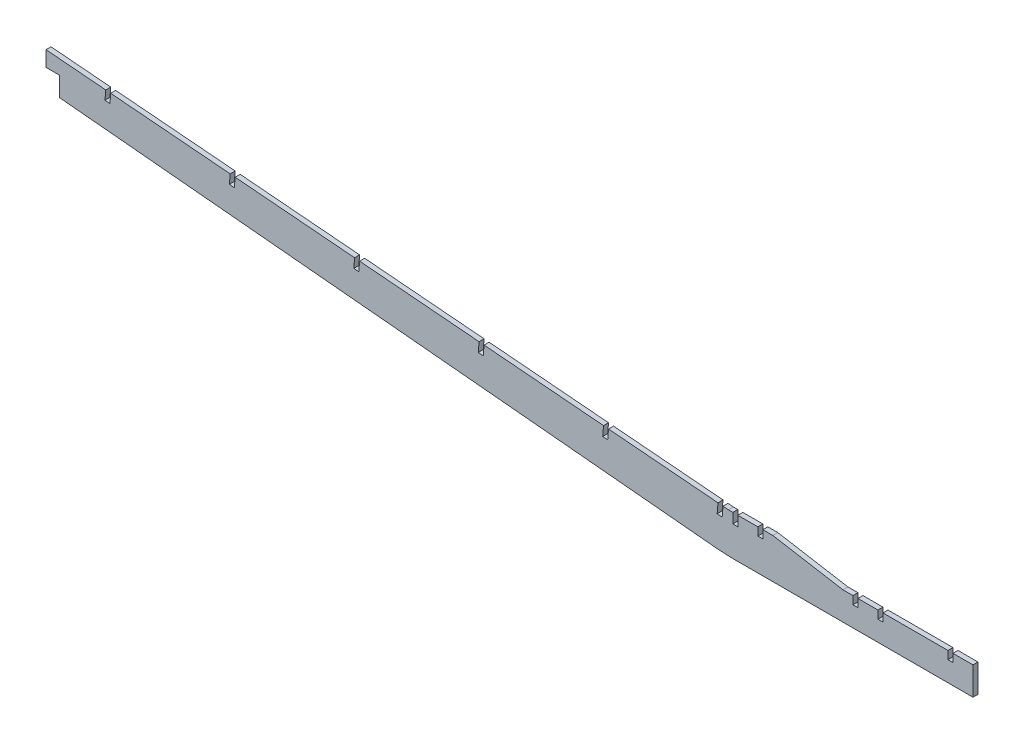
SolidWorks part; units mm, degrees
ref_plane "Front Plane" through (0, 0, 0) normal (0, 0, 1) x (1, 0, 0)
ref_plane "Top Plane" through (0, 0, 0) normal (0, 1, 0) x (1, 0, 0)
ref_plane "Right Plane" through (0, 0, 0) normal (1, 0, 0) x (0, 0, -1)
sketch "Sketch1" plane through (0, 0, 0) normal (0, 0, 1) x (1, 0, 0)
  line L0 (-951.0618, 63.2916) -> (-11.5367, -24.9026)
  line L8 (-8.3728, -25.1683) -> (-6.7788, -6.1851) construction
  line L9 (-6.7788, -6.1851) -> (-9.9426, -5.9194)
  line L10 (-9.9426, -5.9194) -> (-11.5367, -24.9026) construction
  line L11 (-11.5367, -24.9026) -> (-8.3728, -25.1683)
  line L12 (3.175, -25.5459) -> (3.175, -6.4959) construction
  line L13 (3.175, -6.4959) -> (0, -6.4959)
  line L14 (0, -6.4959) -> (0, -25.5459) construction
  line L15 (0, -25.5459) -> (3.175, -25.5459)
  line L17 (-943.9754, 109.7383) -> (-947.3666, 69.3536)
  line L19 (-8.3728, -25.1683) -> (0, -25.5459)
  line L20 (3.175, -25.5459) -> (152.4, -25.5459)
  line L21 (25.4, -0.1459) -> (69.85, -7.7659)
  line L22 (25.4, -0.1459) -> (-2.8123, -0.1459)
  line L23 (-2.8123, -0.1459) -> (-946.5481, 79.1019)
  line L24 (0, -6.4959) -> (0, -0.1459)
  line L25 (3.175, -6.4959) -> (3.175, -0.1459)
  line L26 (-6.7788, -6.1851) -> (-6.2474, 0.1426)
  line L27 (-9.9426, -5.9194) -> (-9.4113, 0.4083)
  line L28 (-9.9426, -5.9194) -> (-946.998, 73.7432)
  line L29 (69.85, -7.7659) -> (152.4, -7.7659)
  line L30 (152.4, -7.7659) -> (152.4, -25.5459)
  line L31 (76.2, -7.7659) -> (76.2, -25.5459)
  line L32 (79.375, -7.7659) -> (79.375, -25.5459)
  line L33 (76.2, -12.8459) -> (79.375, -12.8459)
  line L34 (15.875, -0.1459) -> (15.875, -5.2259)
  line L35 (15.875, -5.2259) -> (19.05, -5.2259)
  line L36 (19.05, -5.2259) -> (19.05, -0.1459)
  line L37 (92.075, -7.7659) -> (92.075, -12.8459)
  line L38 (92.075, -12.8459) -> (95.25, -12.8459)
  line L39 (95.25, -12.8459) -> (95.25, -7.7659)
  line L40 (136.525, -7.7659) -> (136.525, -12.8459)
  line L41 (136.525, -12.8459) -> (139.7, -12.8459)
  line L42 (139.7, -12.8459) -> (139.7, -7.7659)
  line L44 (-951.0618, 63.2916) -> (-950.5305, 69.6193)
  line L45 (-950.5305, 69.6193) -> (-947.3666, 69.3536)
  dimension "D1" = 25.4
  dimension "D2" = 6.35
extrude "Boss-Extrude1" add sketch "Sketch1" along normal blind 3.175 contours L31 L29 L21 L22 L25 L13 L24 L23 L26 L9 L28 L17 L11 L19 L15 L20 | L33 L31 L20 L32 | L29 L32 L20 L30 | L28 L27 L23 L17 | L45 L44 L17 region at (-380.2142, 18.2171, 0) region at (-465.2737, 35.7392, 0) region at (77.7875, -19.1959, 0) region at (115.8875, -16.8176, 0)
sketch "Sketch2" plane through (0, 0, 3.175) normal (0, 0, 1) x (1, 0, 0)
  line L1 (-73.9963, 64.5177) -> (-80.9723, -18.558)
  line L3 (-77.1601, 64.7834) -> (-84.1362, -18.2923)
  line L5 (-153.17, 68.7234) -> (-159.8855, -11.2491)
  line L7 (-232.3428, 72.9404) -> (-238.7996, -3.951)
  line L9 (-311.5203, 77.1018) -> (-317.7101, 3.3887)
  line L11 (-390.6978, 81.2631) -> (-396.6209, 10.7264)
  line L13 (-469.8812, 85.3537) -> (-475.5272, 18.1169)
  line L15 (-549.0652, 89.4374) -> (-554.4332, 25.5108)
  line L17 (-628.256, 93.4393) -> (-633.334, 32.9679)
  line L19 (-707.4489, 97.4177) -> (-712.2332, 40.4425)
  line L21 (-786.6506, 101.2897) -> (-791.1254, 48.0007)
  line L23 (-865.8569, 105.1088) -> (-870.014, 55.603)
  line L25 (-235.5067, 73.2061) -> (-241.9634, -3.6853)
  line L27 (-314.6841, 77.3675) -> (-320.874, 3.6544)
  line L29 (-393.8616, 81.5287) -> (-399.7848, 10.992)
  line L31 (-473.045, 85.6194) -> (-478.6911, 18.3826)
  line L33 (-552.229, 89.7031) -> (-557.5971, 25.7765)
  line L35 (-631.4199, 93.705) -> (-636.4978, 33.2336)
  line L37 (-710.6127, 97.6833) -> (-715.3971, 40.7082)
  line L39 (-789.8145, 101.5554) -> (-794.2893, 48.2664)
  line L41 (-9.9426, -5.9194) -> (-946.998, 73.7432)
  line L43 (-9.4113, 0.4083) -> (-946.5481, 79.1019)
  line L45 (-156.3339, 68.9891) -> (-163.0494, -10.9834)
  line L47 (-869.0207, 105.3745) -> (-873.1778, 55.8686)
  line M13 (-9.4113, 0.4083) -> (-946.5481, 79.1019)
extrude "Cut-Extrude1" cut sketch "Sketch2" against normal through all contours L47 L41 L23 M13 | L41 L21 L39 M13 | L41 L19 L37 M13 | L41 L17 L35 M13 | L41 L15 L33 M13 | L41 L13 L31 M13 | L41 L11 L29 M13 | L41 L9 L27 M13 | L41 L7 L25 M13 | L45 L41 L5 M13 | L41 L1 L3 M13 region at (-80.7341, 3.2483, 3.175) region at (-159.7008, 9.9204, 3.175) region at (-238.6674, 16.5925, 3.175) region at (-317.6341, 23.2647, 3.175) region at (-396.6007, 29.9368, 3.175) region at (-475.5673, 36.6089, 3.175) region at (-554.534, 43.281, 3.175) region at (-633.5006, 49.9532, 3.175) region at (-712.4672, 56.6253, 3.175) region at (-791.4339, 63.2974, 3.175) region at (-870.4005, 69.9696, 3.175)
sketch "Sketch3" plane through (0, 0, 3.175) normal (0, 0, 1) x (1, 0, 0)
  line L0 (-435.837, 36.2162) -> (-435.837, 26.4516)
  line L1 (-397.9339, 33.0334) -> (-473.7401, 39.3991) construction
  line L2 (-435.837, 26.4516) -> (-427.1156, 26.4516)
  line L3 (-427.1156, 26.4516) -> (-427.1156, 14.1082)
  line L4 (-951.0618, 63.2916) -> (-11.5367, -24.9026) construction
  line L5 (-435.837, 36.2162) -> (-981.2137, 132.2658)
  line L6 (-981.2137, 132.2658) -> (-989.3168, 0)
  line L7 (-989.3168, 0) -> (-427.1156, 14.1082)
extrude "Cut-Extrude2" cut sketch "Sketch3" against normal blind 7.62
